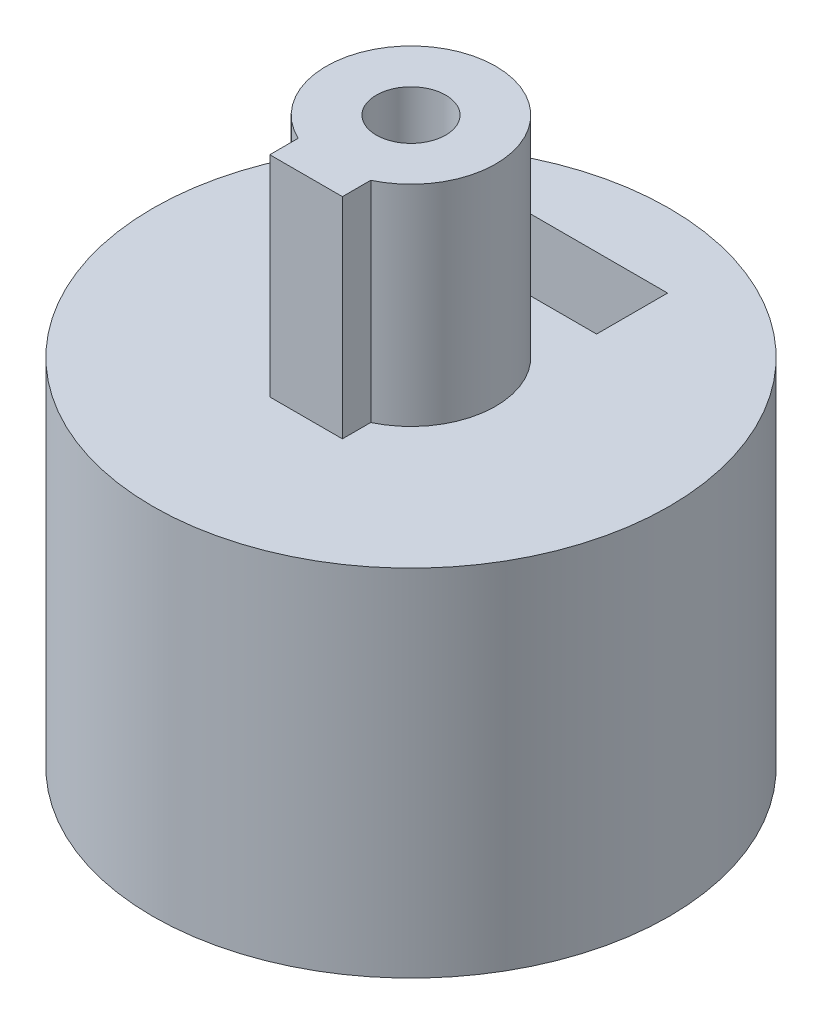
SolidWorks part; units mm, degrees
ref_plane "Front Plane" through (0, 0, 0) normal (0, 0, 1) x (1, 0, 0)
ref_plane "Top Plane" through (0, 0, 0) normal (0, 1, 0) x (1, 0, 0)
ref_plane "Right Plane" through (0, 0, 0) normal (1, 0, 0) x (0, 0, -1)
sketch "Sketch1" plane through (0, 0, 0) normal (0, 1, 0) x (1, 0, 0)
  circle A0 centre (0, 0) radius 1.965 construction
  circle A1 centre (0, 0) radius 8
  dimension "D1" = 3.93
  dimension "D2" = 16
extrude "Boss-Extrude1" add sketch "Sketch1" along normal blind 10
sketch "Sketch2" plane through (0, 0, 0) normal (0, 0, 1) x (1, 0, 0)
  line L0 (0, 10) -> (0, 0) construction
  line L1 (8, 10) -> (-8, 10) construction
  circle A0 centre (0, 7) radius 1.075
  dimension "D1" = 2.15
  dimension "D2" = 3
extrude "Cut-Extrude1" cut sketch "Sketch2" against normal through all
sketch "Sketch4" plane through (0, 0, 0) normal (0, 1, 0) x (1, 0, 0)
  circle A0 centre (0, 0) radius 2.275
  dimension "D1" = 4.55
extrude "Cut-Extrude4" cut sketch "Sketch4" along normal through all
sketch "Sketch5" plane through (0, 10, 0) normal (0, 1, 0) x (1, 0, 0)
  line L0 (-8, 0) -> (8, 0) construction
  line L2 (-0.475, -3.5346) -> (0.475, -3.5346)
  line L3 (-0.475, -3.5346) -> (-0.475, 3.5346)
  line L4 (-0.475, 3.5346) -> (0.475, 3.5346)
  line L5 (0.475, -3.5346) -> (0.475, 3.5346)
  line L6 (0, 3.5346) -> (0, -3.5346) construction
  line L7 (-0.475, 0) -> (0.475, 0) construction
  circle A0 centre (0, 0) radius 8 construction
  point P5 (0, 0)
  dimension "D1" = 0.95
extrude "Boss-Extrude2" add sketch "Sketch5" against normal blind 1.2
sketch "Sketch7" plane through (0, 10, 0) normal (0, 1, 0) x (1, 0, 0)
  circle A0 centre (0, 0) radius 8
  circle A1 centre (0, 0) radius 8 construction
extrude "Boss-Extrude3" add sketch "Sketch7" along normal blind 1
sketch "Sketch8" plane through (0, 11, 0) normal (0, 1, 0) x (1, 0, 0)
  line L0 (0, 0) -> (0, -8) construction
  line L2 (-1.125, -2) -> (1.125, -2)
  line L3 (-1.125, -2) -> (-1.125, -3.25)
  line L4 (-1.125, -3.25) -> (1.125, -3.25)
  line L5 (1.125, -2) -> (1.125, -3.25)
  line L6 (0, -3.25) -> (0, -2) construction
  line L7 (-1.125, -2.625) -> (1.125, -2.625) construction
  circle A0 centre (0, 0) radius 2.625
  circle A1 centre (0, 0) radius 8 construction
  point P3 (0, -2.625)
  dimension "D1" = 5.25
  dimension "D2" = 3.25
  dimension "D3" = 2.25
extrude "Boss-Extrude4" add sketch "Sketch8" along normal blind 6.5 contours A0 L3 L4 L5 | A0 region at (0, 11, 2.8922)
sketch "Sketch9" plane through (0, 17.5, 0) normal (0, 1, 0) x (1, 0, 0)
  circle A0 centre (0, 0) radius 1.075
  dimension "D1" = 2.15
extrude "Cut-Extrude5" cut sketch "Sketch9" against normal blind 6
sketch "Sketch3" plane through (0, 0, 0) normal (0, 0, 1) x (1, 0, 0)
  line L1 (0, 4.4019) -> (2.25, 5.701)
  line L2 (2.25, 5.701) -> (2.25, 8.299)
  line L3 (2.25, 8.299) -> (0, 9.5981) construction
  line L4 (0, 9.5981) -> (-2.25, 8.299) construction
  line L5 (-2.25, 8.299) -> (-2.25, 5.701)
  line L6 (-2.25, 5.701) -> (0, 4.4019)
  line L10 (-2.25, 8.299) -> (2.25, 8.299) construction
  line L11 (-2.25, 8.299) -> (-2.25, 11.4728)
  line L12 (2.25, 8.299) -> (2.25, 11.4728)
  line L13 (-2.25, 11.4728) -> (2.25, 11.4728)
  circle A0 centre (0, 7) radius 2.25 construction
  dimension "D1" = 4.5
extrude "Cut-Extrude2" cut sketch "Sketch3" against normal blind 2.2 from offset 3.5 contours L2 L3 L4 L5 region at (0, 8.2512, 0) offset against normal yes
